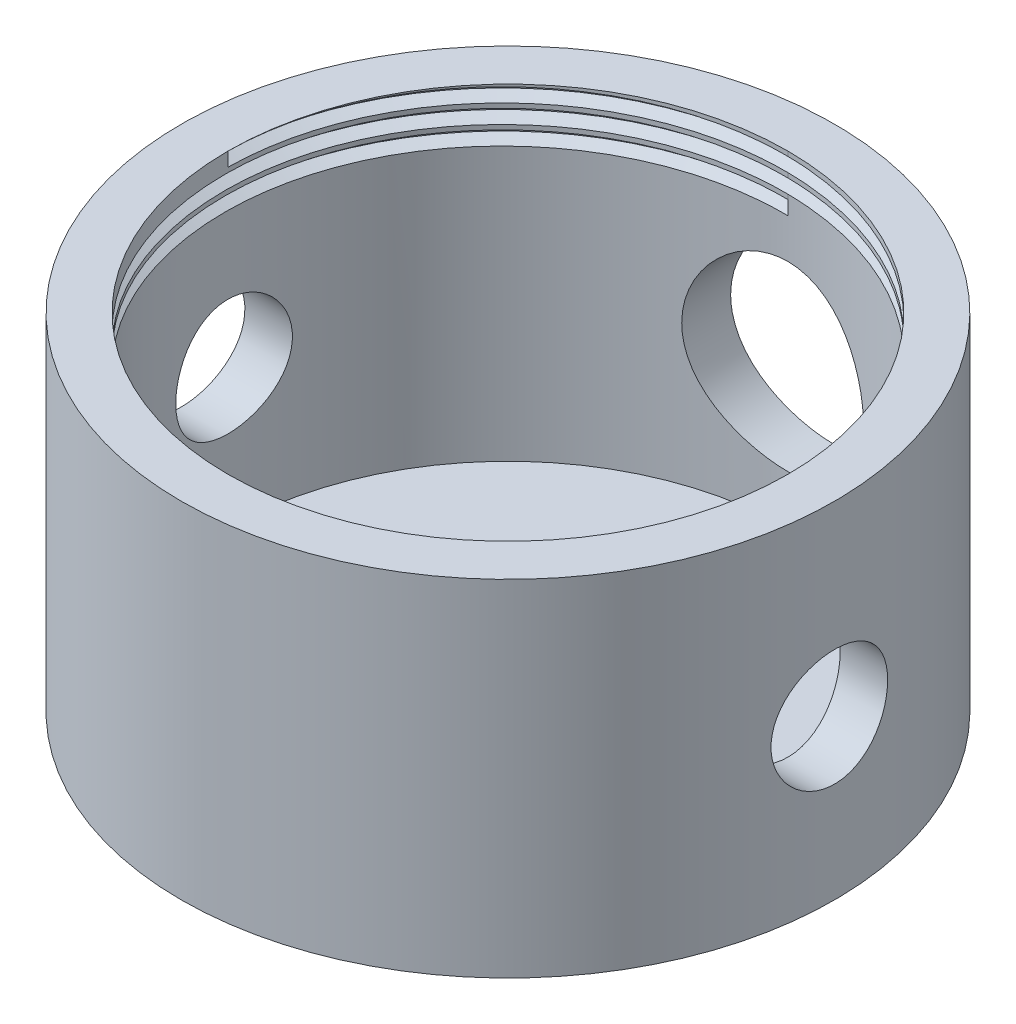
SolidWorks part; units mm, degrees
ref_plane "Front Plane" through (0, 0, 0) normal (0, 0, 1) x (1, 0, 0)
ref_plane "Top Plane" through (0, 0, 0) normal (0, 1, 0) x (1, 0, 0)
ref_plane "Right Plane" through (0, 0, 0) normal (1, 0, 0) x (0, 0, -1)
sketch "Sketch1" plane through (0, 0, 0) normal (0, 1, 0) x (1, 0, 0)
  circle A0 centre (0, 0) radius 35
  dimension "D1" = 70
extrude "Boss-Extrude1" add sketch "Sketch1" along normal blind 2 contours A0
sketch "Sketch2" plane through (0, 2, 0) normal (0, 1, 0) x (1, 0, 0)
  circle A0 centre (0, 0) radius 35
  circle A1 centre (0, 0) radius 30
  dimension "D1" = 70
  dimension "D2" = 5
extrude "Boss-Extrude2" add sketch "Sketch2" along normal blind 35
ref_plane "Plane3" through (0, 0, 40) normal (0, 0, 1) x (1, 0, 0)
sketch "Sketch5" plane through (0, 0, 40) normal (0, 0, 1) x (1, 0, 0)
  line L0 (-35, 0) -> (35, 0) construction
  line L1 (-26.6422, 0) -> (27.3578, 0)
  line L2 (-26.6422, 0) -> (-26.6422, -34)
  line L3 (-26.6422, -34) -> (27.3578, -34)
  line L4 (27.3578, 0) -> (27.3578, -34)
  line L5 (-35, 0) -> (35, 0) construction
  line L6 (-24.6422, -2) -> (25.3578, -2)
  line L7 (-24.6422, -2) -> (-24.6422, -32)
  line L8 (-24.6422, -32) -> (25.3578, -32)
  line L9 (25.3578, -2) -> (25.3578, -32)
  dimension "D1" = 2
  dimension "D2" = 2
  dimension "D3" = 2
  dimension "D4" = 2
  dimension "D5" = 50
  dimension "D6" = 2
  dimension "D7" = 30
thread "Thread1" pitch 2 method cut profile "Thread Profile1" start angle 0, offset 0, length 4.5, pitch 2, diameter 60
ref_plane "Plane4" through (-30, 37, 0) normal (0, 0, 1) x (-1, 0, 0)
sketch "Thread Profile1" plane through (-30, 37, 0) normal (0, 0, 1) x (-1, 0, 0)
  line L0 (0, 0) -> (0, 2) construction
  line L1 (0, 0) -> (1.0825, 0.625)
  line L2 (1.0825, 0.625) -> (1.0825, 0.875)
  line L3 (1.0825, 0.875) -> (0, 1.5)
  line L4 (1.0825, 0.75) -> (0, 0.75) construction
  line L11 (0, 0) -> (0, 1.5)
  point P2 (0, 0)
  dimension "Pitch" = 2
  dimension "Profile_Angle" = 60
  dimension "Profile_Land" = 0.25
  dimension "Profile_Height" = 1.0825
ref_plane "Plane6" through (0, 0, -35) normal (0, 0, -1) x (-1, 0, 0)
sketch "Sketch10" plane through (0, 0, -35) normal (0, 0, -1) x (-1, 0, 0)
  line L0 (0, 17) -> (-42.3594, 17) construction
  line L1 (0, 37) -> (0, 0) construction
  line L2 (35, 37) -> (-35, 37) construction
  line L3 (-42.3594, 17) -> (37.1989, 17) construction
  circle A1 centre (0, 17) radius 9.75
  dimension "D2" = 19.5
  dimension "D5" = 37
  dimension "D6" = 20
extrude "Cut-Extrude2" cut sketch "Sketch10" against normal up to next
ref_plane "Plane8" through (-35, 0, 0) normal (-1, 0, 0) x (0, 0, 1)
sketch "Sketch12" plane through (-35, 0, 0) normal (-1, 0, 0) x (0, 0, 1)
  line L1 (35, 37) -> (-35, 37) construction
  circle A0 centre (0, 17) radius 6.25
  dimension "D1" = 12.5
  dimension "D2" = 20
extrude "Cut-Extrude4" cut sketch "Sketch12" against normal up to next
ref_plane "Plane9" through (35, 0, 0) normal (1, 0, 0) x (0, 0, -1)
sketch "Sketch13" plane through (35, 0, 0) normal (1, 0, 0) x (0, 0, -1)
  line L0 (35, 37) -> (-35, 37) construction
  circle A0 centre (0, 17) radius 6.25
  dimension "D1" = 12.5
  dimension "D2" = 20
extrude "Cut-Extrude5" cut sketch "Sketch13" against normal up to next
sketch "Sketch14" plane through (0, 2, 0) normal (0, 1, 0) x (1, 0, 0)
  circle A0 centre (0, 0) radius 6
  dimension "D1" = 12
extrude "Cut-Extrude6" cut sketch "Sketch14" against normal up to next
